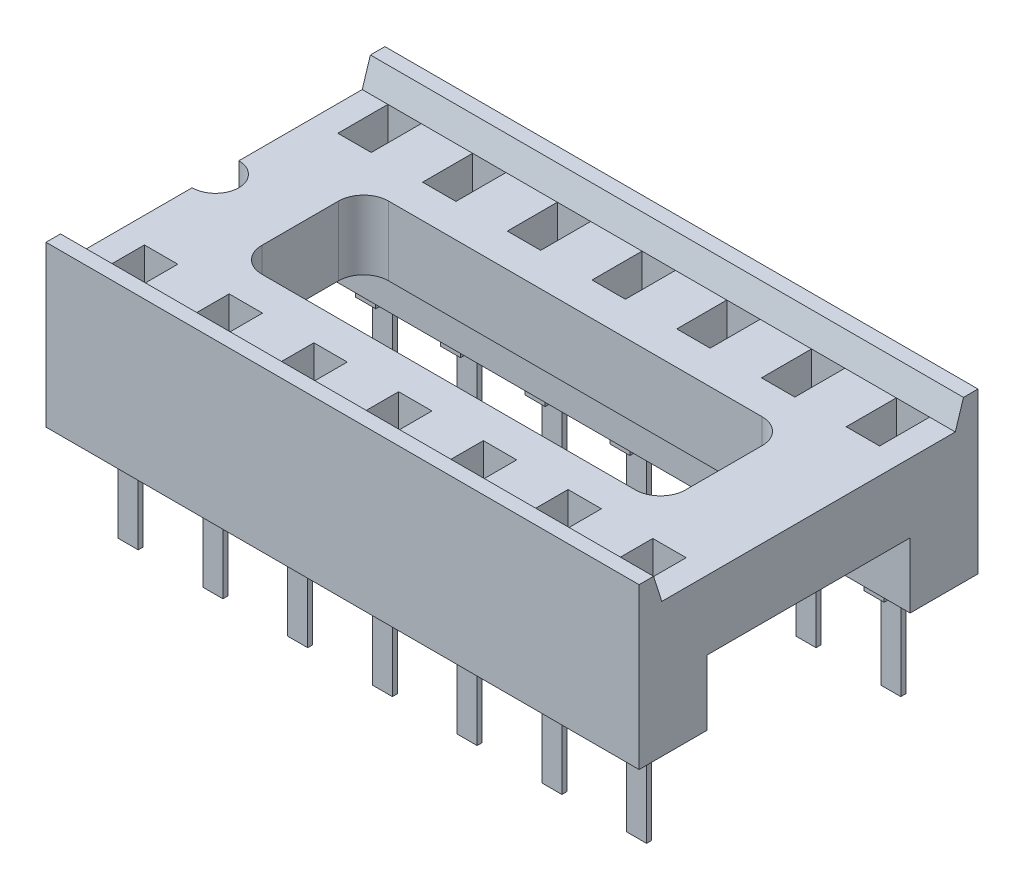
SolidWorks part; units mm, degrees
ref_plane "Front" through (0, 0, 0) normal (0, 0, 1) x (1, 0, 0)
ref_plane "Top" through (0, 0, 0) normal (0, 1, 0) x (1, 0, 0)
ref_plane "Right" through (0, 0, 0) normal (1, 0, 0) x (0, 0, -1)
sketch "Эскиз2" plane through (0, 0, 0) normal (1, 0, 0) x (0, 0, -1)
  line L0 (0, 12.1599) -> (0, -12.1599) construction
  line L1 (-8.6828, 0) -> (8.3721, 0) construction
  line L2 (-4.3996, 4.025) -> (4.3996, 4.025)
  line L3 (4.3996, 4.025) -> (4.6448, 4.8)
  line L4 (4.6448, 4.8) -> (5.08, 4.8)
  line L5 (5.08, 4.8) -> (5.08, 0)
  line L6 (5.08, 0) -> (3.735, 0)
  line L7 (3.735, 0) -> (3.735, -0.3)
  line L8 (3.735, -0.3) -> (3.235, -0.3)
  line L9 (3.235, -0.3) -> (3.235, 0)
  line L10 (3.235, 0) -> (3.0456, 0)
  line L11 (3.735, -0.3) -> (3.735, -3)
  line L12 (3.735, -3) -> (3.885, -3)
  line L13 (3.885, -3) -> (3.885, 0)
  line L14 (-3.885, -3) -> (-3.885, 0)
  line L15 (-3.735, -3) -> (-3.885, -3)
  line L16 (-3.735, -0.3) -> (-3.735, -3)
  line L17 (-3.235, -0.3) -> (-3.235, 0)
  line L18 (-3.735, -0.3) -> (-3.235, -0.3)
  line L19 (-3.735, 0) -> (-3.735, -0.3)
  line L20 (-5.08, 0) -> (-3.735, 0)
  line L21 (-5.08, 4.8) -> (-5.08, 0)
  line L22 (-4.6448, 4.8) -> (-5.08, 4.8)
  line L23 (-4.3996, 4.025) -> (-4.6448, 4.8)
  line L24 (3.0456, 0) -> (3.0456, 1.9542)
  line L25 (3.0456, 1.9542) -> (-3.0456, 1.9542)
  line L26 (-3.235, 0) -> (-3.0456, 0)
  line L27 (-3.0456, 0) -> (-3.0456, 1.9542)
  point P16 (4.4075, 0)
  point P18 (3.81, -3)
  point P28 (0, 0)
  point P34 (0, 4.025)
  point P38 (0, 1.9542)
  dimension "D1" = 5.08
  dimension "D2" = 4.8
  dimension "D3" = 0.3
  dimension "D4" = 0.15
  dimension "D5" = 3.81
  dimension "D6" = 0.5
  dimension "D7" = 3
extrude "Бобышка-Вытянуть1" add sketch "Эскиз2" along normal mid plane 17.78 contours L20 L14 L15 L16 L19 | L12 L13 L6 L7 L11 | L2 L23 L22 L21 L20 L19 L18 L17 L9 L8 L7 L6 L5 L4 L3 region at (0, 2.4677, 0) region at (0, -1.5, 3.81) region at (0, -1.5, -3.81)
sketch "Эскиз3" plane through (0, 4.025, 0) normal (0, 1, 0) x (1, 0, 0)
  line L0 (-9.7214, 0) -> (9.9853, 0) construction
  line L1 (-8.89, -4.3996) -> (-8.89, 4.3996) construction
  line L2 (-8.12, 4.3996) -> (-8.12, 2.8996)
  line L3 (8.89, 4.3996) -> (-8.89, 4.3996) construction
  line L4 (-8.12, 2.8996) -> (-7.12, 2.8996)
  line L5 (-7.12, 2.8996) -> (-7.12, 4.3996)
  line L6 (-7.12, 4.3996) -> (-8.12, 4.3996)
  line L7 (-5.58, 4.3996) -> (-5.58, 2.8996)
  line L8 (-5.58, 2.8996) -> (-4.58, 2.8996)
  line L9 (-4.58, 2.8996) -> (-4.58, 4.3996)
  line L10 (-4.58, 4.3996) -> (-5.58, 4.3996)
  line L11 (-3.04, 4.3996) -> (-3.04, 2.8996)
  line L12 (-3.04, 2.8996) -> (-2.04, 2.8996)
  line L13 (-2.04, 2.8996) -> (-2.04, 4.3996)
  line L14 (-2.04, 4.3996) -> (-3.04, 4.3996)
  line L15 (-0.5, 4.3996) -> (-0.5, 2.8996)
  line L16 (-0.5, 2.8996) -> (0.5, 2.8996)
  line L17 (0.5, 2.8996) -> (0.5, 4.3996)
  line L18 (0.5, 4.3996) -> (-0.5, 4.3996)
  line L19 (2.04, 4.3996) -> (2.04, 2.8996)
  line L20 (2.04, 2.8996) -> (3.04, 2.8996)
  line L21 (3.04, 2.8996) -> (3.04, 4.3996)
  line L22 (3.04, 4.3996) -> (2.04, 4.3996)
  line L23 (4.58, 4.3996) -> (4.58, 2.8996)
  line L24 (4.58, 2.8996) -> (5.58, 2.8996)
  line L25 (5.58, 2.8996) -> (5.58, 4.3996)
  line L26 (5.58, 4.3996) -> (4.58, 4.3996)
  line L27 (7.12, 4.3996) -> (7.12, 2.8996)
  line L28 (7.12, 2.8996) -> (8.12, 2.8996)
  line L29 (8.12, 2.8996) -> (8.12, 4.3996)
  line L30 (8.12, 4.3996) -> (7.12, 4.3996)
  line L31 (-6.35, -1.1496) -> (-6.35, 1.1496)
  line L32 (8.12, -4.3996) -> (7.12, -4.3996)
  line L33 (8.12, -2.8996) -> (8.12, -4.3996)
  line L34 (7.12, -2.8996) -> (8.12, -2.8996)
  line L35 (7.12, -4.3996) -> (7.12, -2.8996)
  line L36 (5.58, -4.3996) -> (4.58, -4.3996)
  line L37 (5.58, -2.8996) -> (5.58, -4.3996)
  line L38 (4.58, -2.8996) -> (5.58, -2.8996)
  line L39 (4.58, -4.3996) -> (4.58, -2.8996)
  line L40 (3.04, -4.3996) -> (2.04, -4.3996)
  line L41 (3.04, -2.8996) -> (3.04, -4.3996)
  line L42 (2.04, -2.8996) -> (3.04, -2.8996)
  line L43 (2.04, -4.3996) -> (2.04, -2.8996)
  line L44 (0.5, -4.3996) -> (-0.5, -4.3996)
  line L45 (0.5, -2.8996) -> (0.5, -4.3996)
  line L46 (-0.5, -2.8996) -> (0.5, -2.8996)
  line L47 (-0.5, -4.3996) -> (-0.5, -2.8996)
  line L48 (-2.04, -4.3996) -> (-3.04, -4.3996)
  line L49 (-2.04, -2.8996) -> (-2.04, -4.3996)
  line L50 (-3.04, -2.8996) -> (-2.04, -2.8996)
  line L51 (-3.04, -4.3996) -> (-3.04, -2.8996)
  line L52 (-4.58, -4.3996) -> (-5.58, -4.3996)
  line L53 (-4.58, -2.8996) -> (-4.58, -4.3996)
  line L54 (-5.58, -2.8996) -> (-4.58, -2.8996)
  line L55 (-5.58, -4.3996) -> (-5.58, -2.8996)
  line L56 (-7.12, -4.3996) -> (-8.12, -4.3996)
  line L57 (-7.12, -2.8996) -> (-7.12, -4.3996)
  line L58 (-8.12, -2.8996) -> (-7.12, -2.8996)
  line L59 (-8.12, -4.3996) -> (-8.12, -2.8996)
  line L60 (-5.6, 1.8996) -> (5.6, 1.8996)
  line L61 (6.35, 1.1496) -> (6.35, -1.1496)
  line L62 (-5.6, -1.8996) -> (5.6, -1.8996)
  line L63 (-8.89, 0.7) -> (-8.89, -0.7)
  arc A0 (-8.89, 0.7) -> (-8.89, -0.7) centre (-8.89, 0) cw
  arc A1 (5.6, 1.8996) -> (6.35, 1.1496) centre (5.6, 1.1496) cw
  arc A2 (-6.35, 1.1496) -> (-5.6, 1.8996) centre (-5.6, 1.1496) cw
  arc A3 (5.6, -1.8996) -> (6.35, -1.1496) centre (5.6, -1.1496) ccw
  arc A4 (-6.35, -1.1496) -> (-5.6, -1.8996) centre (-5.6, -1.1496) ccw
  point P14 (-7.62, 2.8996)
  point P71 (7.62, 2.8996)
  point P78 (6.35, 0)
  point P83 (-6.35, 0)
  line M1 (-8.89, 4.3996) -> (-8.89, -4.3996)
  line M2 (-8.89, -4.3996) -> (8.89, -4.3996)
  line M4 (8.89, 4.3996) -> (-8.89, 4.3996)
  dimension "D1" = 0.7
  dimension "D9" = 0.75
  dimension "D2" = 1
  dimension "D3" = 1.27
  dimension "D4" = 1.5
  dimension "D6" = 1.27
  dimension "D7" = 1.27
  dimension "D8" = 1
  dimension "D5" = 7
extrude "Вырез-Вытянуть1" cut sketch "Эскиз3" against normal up to next contours L0 L63 A0 | L0 A0 M1 region at (-8.5929, 4.025, -0.2971) region at (-8.5929, 4.025, 0.2971)
extrude "Вырез-Вытянуть2" cut sketch "Эскиз3<3>" against normal up to next contours L0 L31 A4 L62 A3 L61 | L31 L0 L61 A1 L60 A2 region at (0, 4.025, -0.9419) region at (0, 4.025, 0.9419)
sketch "Эскиз3<3>" plane through (0, 4.025, 0) normal (0, 1, 0) x (1, 0, 0) same geometry as "Эскиз3"
extrude "Вырез-Вытянуть3" cut sketch "Эскиз3<4>" against normal blind 1 contours L4 L5 L2 M4 | L8 L9 L7 M4 | L12 L13 L11 M4 | L16 L17 L15 M4 | L20 L21 L19 M4 | L24 L25 L23 M4 | L28 L29 L27 M4 | L35 L33 L34 M2 | L39 L37 L38 M2 | L43 L41 L42 M2 | L47 L45 L46 M2 | L51 L49 L50 M2 | L55 L53 L54 M2 | L59 L57 L58 M2 region at (-7.62, 4.025, -3.6496) region at (7.62, 4.025, -3.6496) region at (5.08, 4.025, -3.6496) region at (2.54, 4.025, -3.6496) region at (0, 4.025, -3.6496) region at (-2.54, 4.025, -3.6496) region at (-5.08, 4.025, -3.6496) region at (-7.62, 4.025, 3.6496) region at (-5.08, 4.025, 3.6496) region at (-2.54, 4.025, 3.6496) region at (0, 4.025, 3.6496) region at (2.54, 4.025, 3.6496) region at (5.08, 4.025, 3.6496) region at (7.62, 4.025, 3.6496)
sketch "Эскиз3<4>" plane through (0, 4.025, 0) normal (0, 1, 0) x (1, 0, 0) same geometry as "Эскиз3"
sketch "Эскиз4" plane through (0, 0, 3.885) normal (0, 0, 1) x (1, 0, 0)
  line L0 (-7.92, 0) -> (-7.92, -3)
  line L1 (8.89, 0) -> (-8.89, 0) construction
  line L2 (8.89, -3) -> (-8.89, -3) construction
  line L4 (-7.92, 0) -> (-7.32, 0)
  line L5 (-7.32, -3) -> (-7.32, 0)
  line L6 (8.89, 0) -> (-8.89, 0) construction
  line L7 (-7.92, -3) -> (-7.32, -3)
  line L8 (-8.89, -3) -> (-8.89, 0) construction
  line L9 (-5.38, 0) -> (-5.38, -3)
  line L10 (-5.38, 0) -> (-4.78, 0)
  line L11 (-4.78, -3) -> (-4.78, 0)
  line L12 (-5.38, -3) -> (-4.78, -3)
  line L13 (-2.84, 0) -> (-2.84, -3)
  line L14 (-2.84, 0) -> (-2.24, 0)
  line L15 (-2.24, -3) -> (-2.24, 0)
  line L16 (-2.84, -3) -> (-2.24, -3)
  line L17 (-0.3, 0) -> (-0.3, -3)
  line L18 (-0.3, 0) -> (0.3, 0)
  line L19 (0.3, -3) -> (0.3, 0)
  line L20 (-0.3, -3) -> (0.3, -3)
  line L21 (2.24, 0) -> (2.24, -3)
  line L22 (2.24, 0) -> (2.84, 0)
  line L23 (2.84, -3) -> (2.84, 0)
  line L24 (2.24, -3) -> (2.84, -3)
  line L25 (4.78, 0) -> (4.78, -3)
  line L26 (4.78, 0) -> (5.38, 0)
  line L27 (5.38, -3) -> (5.38, 0)
  line L28 (4.78, -3) -> (5.38, -3)
  line L29 (7.32, 0) -> (7.32, -3)
  line L30 (7.32, 0) -> (7.92, 0)
  line L31 (7.92, -3) -> (7.92, 0)
  line L32 (7.32, -3) -> (7.92, -3)
  line L33 (-8.89, 0) -> (8.89, 0)
  line L34 (8.89, 0) -> (8.89, -3)
  line L35 (8.89, -3) -> (-8.89, -3)
  line L36 (-8.89, -3) -> (-8.89, 0)
  point P5 (-7.62, -3)
  line M33 (-8.89, 0) -> (-8.89, -3)
  line M34 (-8.89, -3) -> (8.89, -3)
  line M35 (8.89, -3) -> (8.89, 0)
  line M36 (8.89, 0) -> (-8.89, 0)
  dimension "D1" = 0.6
  dimension "D2" = 1.27
  dimension "D3" = 7
extrude "Вырез-Вытянуть4" cut sketch "Эскиз4" against normal through all contours L0 M36 M33 M34 | L9 L5 M36 M34 | L13 L11 M36 M34 | L17 L15 M36 M34 | L21 L19 M36 M34 | L25 L23 M36 M34 | L29 L27 M36 M34 | L31 M34 M35 M36 region at (-8.405, -1.5, 3.885) region at (-6.35, -1.5, 3.885) region at (-3.81, -1.5, 3.885) region at (-1.27, -1.5, 3.885) region at (1.27, -1.5, 3.885) region at (3.81, -1.5, 3.885) region at (6.35, -1.5, 3.885) region at (8.405, -1.5, 3.885)
